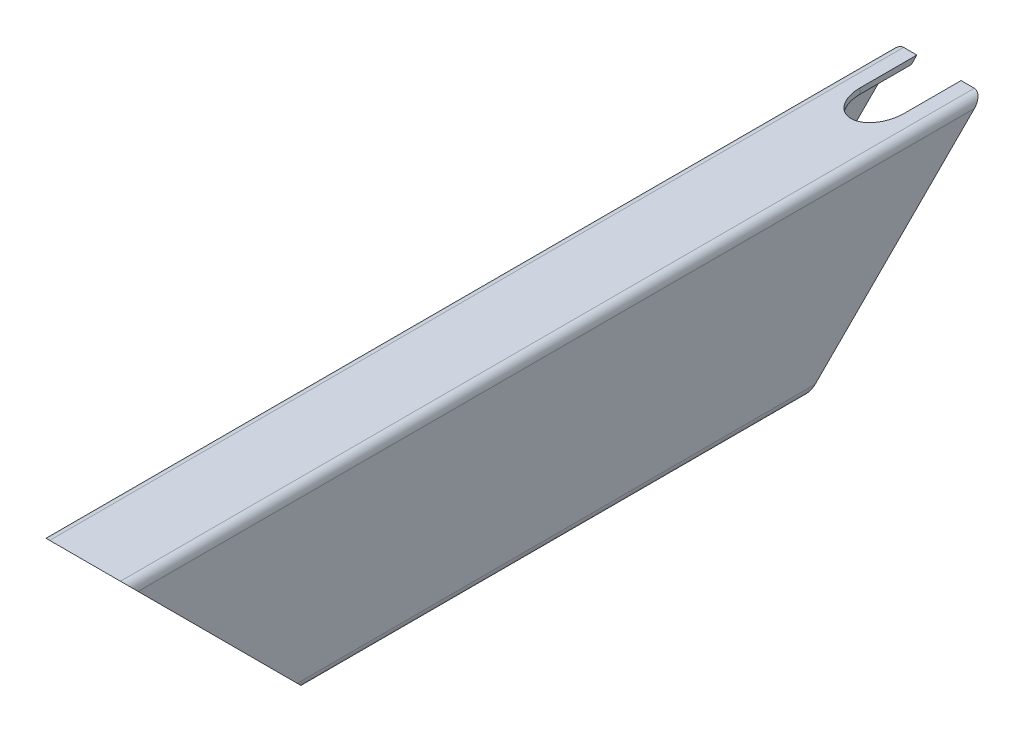
SolidWorks part; units mm, degrees
material "6061-T6 (SS)"
ref_plane "Front" through (0, 0, 0) normal (0, 0, 1) x (1, 0, 0)
ref_plane "Top" through (0, 0, 0) normal (0, 1, 0) x (1, 0, 0)
ref_plane "Right" through (0, 0, 0) normal (1, 0, 0) x (0, 0, -1)
sketch "Sketch3" plane through (0, 0, 0) normal (1, 0, 0) x (0, 0, -1)
  line L0 (-50.8, -25.4) -> (-194.4841, -25.4)
  line L1 (-194.4841, -25.4) -> (-245.2841, 25.4)
  line L2 (-245.2841, 25.4) -> (0, 25.4)
  line L3 (0, 25.4) -> (-50.8, -25.4)
  point P8 (-25.4, 0)
  dimension "D1" = 50.8
  dimension "D2" = 101.6
  dimension "D3" = 45
sketch "Sketch1" plane through (0, 0, 0) normal (0, 0, 1) x (1, 0, 0)
  line L1 (-10.16, -25.4) -> (10.16, -25.4)
  line L2 (-12.7, -22.86) -> (-12.7, 22.86)
  line L3 (-10.16, 25.4) -> (10.16, 25.4)
  line L4 (12.7, -22.86) -> (12.7, 22.86)
  line L5 (-12.7, -25.4) -> (12.7, 25.4) construction
  line L6 (-12.7, 25.4) -> (12.7, -25.4) construction
  arc A0 (-10.16, -25.4) -> (-12.7, -22.86) centre (-10.16, -22.86) cw
  arc A1 (10.16, -25.4) -> (12.7, -22.86) centre (10.16, -22.86) ccw
  arc A2 (10.16, 25.4) -> (12.7, 22.86) centre (10.16, 22.86) cw
  arc A3 (-12.7, 22.86) -> (-10.16, 25.4) centre (-10.16, 22.86) cw
  point P0 (0, 0)
  dimension "D3" = 2.54
  dimension "D1" = 25.4
  dimension "D2" = 50.8
extrude "Extrude-Thin1" add sketch "Sketch1" along normal up to vertex (245.2841 mm away) thin up to point (0, 25.4, 245.2841) thin type one direction reverse wall 1.5875
sketch "Sketch2" plane through (12.7, 0, 0) normal (1, 0, 0) x (0, 0, -1)
  line L0 (-245.2841, 25.4) -> (-194.4841, -25.4)
  line L1 (-245.2841, -25.4) -> (0, -25.4) construction
  line L2 (-194.4841, -25.4) -> (-245.2841, -25.4)
  line L3 (-245.2841, -25.4) -> (-245.2841, 25.4)
  line L4 (0, 25.4) -> (-50.8, -25.4)
  line L5 (-50.8, -25.4) -> (0, -25.4)
  line L6 (0, -25.4) -> (0, 25.4)
  line L7 (0, 25.4) -> (-50.8, -25.4) construction
  line L8 (-194.4841, -25.4) -> (-245.2841, 25.4) construction
extrude "Cut-Extrude1" cut sketch "Sketch2" against normal through all
sketch "Sketch4" plane through (0, 12.7, 12.7) normal (0, -0.7071, -0.7071) x (1, 0, 0)
  circle A0 centre (0, -22.3185) radius 6.35
  circle A1 centre (0, -6.4435) radius 6.35
  circle A2 centre (0, -38.1935) radius 6.35
  dimension "D1" = 12.7
extrude "Cut-Extrude2" cut sketch "Sketch4" against normal through all
sketch "Sketch5" plane through (0, 25.4, 0) normal (0, 1, 0) x (1, 0, 0)
  line L0 (-6.35, -16.2876) -> (-6.35, 0)
  line L1 (-6.35, 0) -> (6.35, 0)
  line L2 (6.35, 0) -> (6.35, -16.2876)
  line L3 (-4.6185, 0) -> (-10.16, 0) construction
  ellipse E1 centre (0, -16.2876) end of major axis (0, -7.3073) minor radius 6.35 construction
  ellipse E3 centre (0, -16.2876) end of major axis (0, -7.3073) minor radius 6.35 (-6.35, -16.2876) -> (6.35, -16.2876) ccw
  point P0 (6.35, -19.6221)
extrude "Cut-Extrude3" cut sketch "Sketch5" against normal through all
